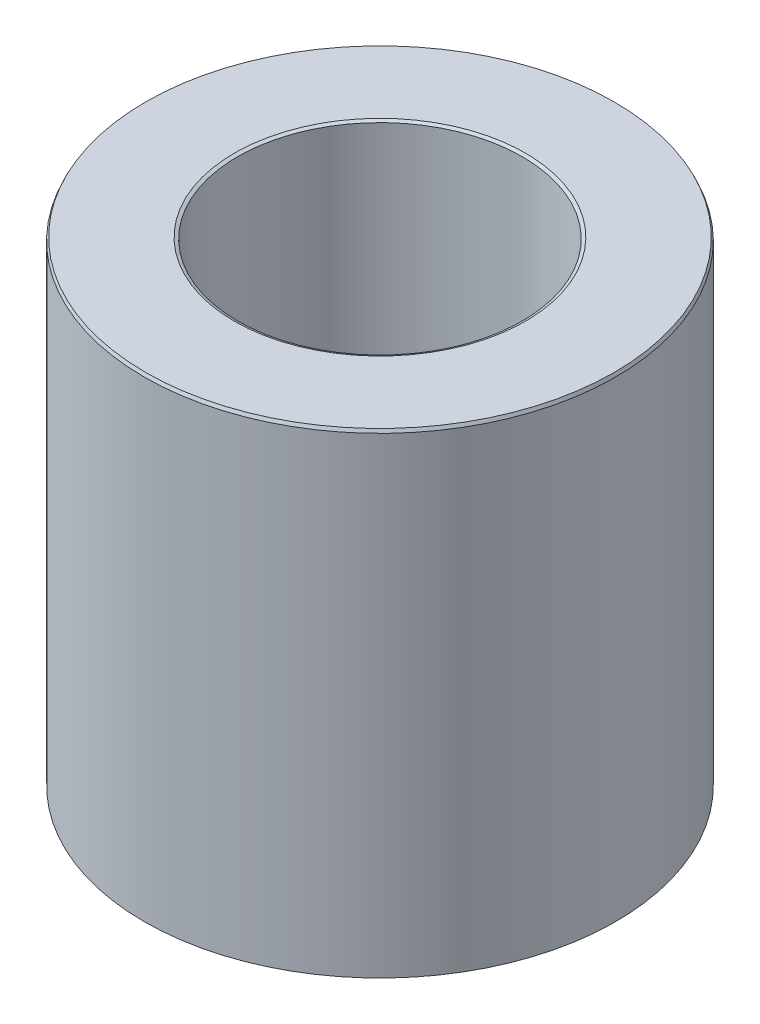
SolidWorks part; units mm, degrees
ref_plane "Front Plane" through (0, 0, 0) normal (0, 0, 1) x (1, 0, 0)
ref_plane "Top Plane" through (0, 0, 0) normal (0, 1, 0) x (1, 0, 0)
ref_plane "Right Plane" through (0, 0, 0) normal (1, 0, 0) x (0, 0, -1)
sketch "Sketch1" plane through (0, 0, 0) normal (0, 1, 0) x (1, 0, 0)
  circle A0 centre (0, 0) radius 60
  dimension "SLEEVE_OD" = 120
extrude "Boss-Extrude1" add sketch "Sketch1" along normal blind 121.2516
sketch "Sketch2" plane through (0, 0, 0) normal (0, 1, 0) x (1, 0, 0)
  circle A0 centre (0, 0) radius 36.2327
  dimension "BORE_D" = 72.4654
extrude "Cut-Extrude1" cut sketch "Sketch2" along normal through all
chamfer "Chamfer1" distance 0.8236 angle 23.807 4 edges at (0, 121.2516, 36.2327) (0, 0, 36.2327) (0, 0, 60) (0, 121.2516, 60) first distance on face at (0, 121.2516, 36.2327) first distance on face at (0, 0, 36.2327) first distance on face at (0, 121.2516, 60)
